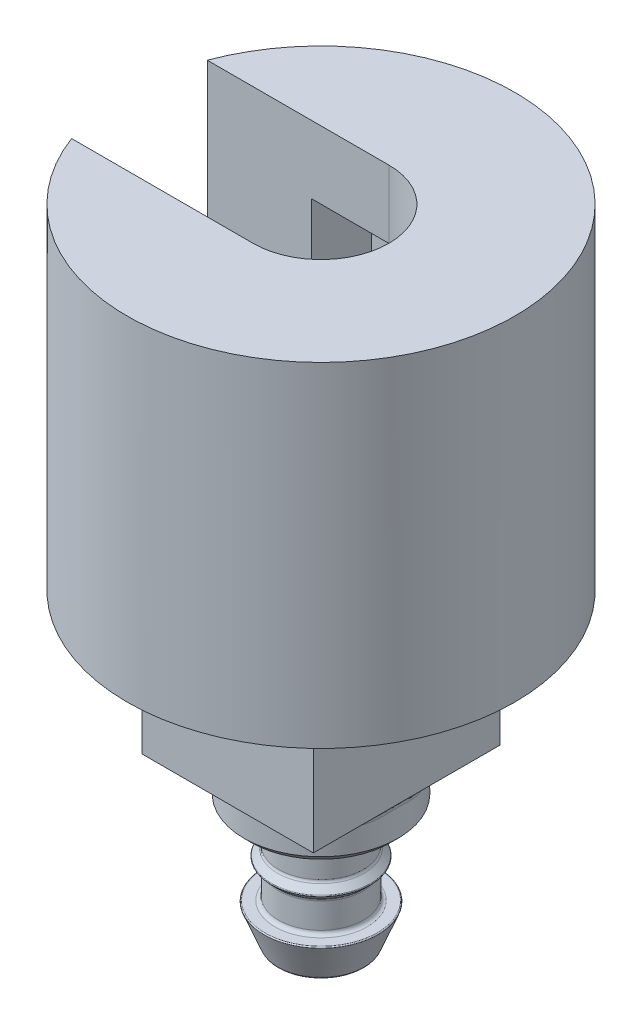
SolidWorks part; units mm, degrees
ref_plane "Front Plane" through (0, 0, 0) normal (0, 0, 1) x (1, 0, 0)
ref_plane "Top Plane" through (0, 0, 0) normal (0, 1, 0) x (1, 0, 0)
ref_plane "Right Plane" through (0, 0, 0) normal (1, 0, 0) x (0, 0, -1)
sketch "Sketch1" plane through (0, 0, 0) normal (0, 0, 1) x (1, 0, 0)
  line L0 (0, 1017.6623) -> (0, 12.7) construction
  line L1 (0, -12.7) -> (4.3656, -12.7)
  line L3 (4.3656, 0) -> (7.9375, 0)
  line L4 (7.9375, 0) -> (7.9375, 3.9688)
  line L8 (0, 3.9688) -> (0, -12.7)
  line L9 (4.3656, -12.7) -> (5.9531, -8.7312)
  line L22 (7.9375, 0) -> (7.9375, 3.9688) construction
  line L25 (7.9375, 6.35) -> (0, 6.35) construction
  line L27 (6.35, 3.9688) -> (7.9375, 3.9688)
  line L32 (5.9531, -8.7312) -> (4.3656, -8.7312)
  line L33 (4.3656, -8.7312) -> (4.3656, -5.5563)
  line L34 (4.3656, -3.9687) -> (5.1594, -4.7625)
  line L35 (5.1594, -4.7625) -> (4.3656, -5.5563)
  line L36 (5.1594, -4.7625) -> (4.3656, -4.7625) construction
  line L37 (4.3656, -3.9687) -> (4.3656, 0)
  line L38 (6.35, 3.9688) -> (0, 3.9688)
  line L40 (0, 3.9688) -> (0, -7.7377) construction
  dimension "D7" = 1.5875
  dimension "D1" = 12.7
  dimension "D2" = 3.9688
  dimension "D6" = 15.875
  dimension "D8" = 8.7312
  dimension "D10" = 7.9375
  dimension "D11" = 45
  dimension "D9" = 0.7937
revolve "Revolve1" add sketch "Sketch1" angle 360 about L0
fillet "Fillet3" radius 0.3969 5 edges at (0, -12.7, 4.3656) (0, -8.7313, 4.3656) (0, 0, 4.3656) (0, -3.9688, 4.3656) (0, -5.5562, 4.3656)
fillet "Fillet4" radius 0.0992 2 edges at (0, -8.7313, 5.9531) (0, -4.7625, 5.1594)
ref_plane "Plane1" through (0, 3.9688, 0) normal (0, 1, 0) x (1, 0, 0)
sketch "Sketch2" plane through (0, 3.9688, 0) normal (0, 1, 0) x (1, 0, 0)
  line L0 (0, 9.6273) -> (0, -9.6273) construction
  line L9 (9.0227, 0) -> (-9.0227, 0) construction
  line L11 (8.8366, 9.6273) -> (-8.8366, 9.6273)
  line L12 (8.8366, 9.6273) -> (8.8366, -9.6273)
  line L13 (8.8366, -9.6273) -> (-8.8366, -9.6273)
  line L14 (-8.8366, 9.6273) -> (-8.8366, -9.6273)
  line L15 (8.8366, 9.6273) -> (-8.8366, -9.6273) construction
  line L16 (8.8366, -9.6273) -> (-8.8366, 9.6273) construction
  point P0 (0, 0)
  point P1 (0, 0)
  point P2 (0, 0)
  point P6 (0, 0)
  point P11 (0, 0)
extrude "Boss-Extrude1" add sketch "Sketch2" along normal blind 15
sketch "Sketch3" plane through (0, -12.7, 0) normal (0, -1, 0) x (1, 0, 0)
  circle A0 centre (0, 0) radius 2.413
extrude "Cut-Extrude1" cut sketch "Sketch3" against normal blind 27
sketch "Sketch5" plane through (0, 0, 0) normal (1, 0, 0) x (0, 0, -1)
  line L0 (0, 18.9688) -> (0, 3.9688) construction
  line L1 (9.6273, 18.9688) -> (-9.6273, 18.9688) construction
  line L2 (55, 3.9688) -> (-55, 3.9688) construction
  circle A0 centre (0, 11.4688) radius 2.25
  dimension "D1" = 4.5
extrude "Cut-Extrude3" cut sketch "Sketch5" against normal blind 22.86
chamfer "Chamfer2" distance 0.762 angle 45 5 edges at (8.8366, 3.9688, 0) (0, 3.9688, -9.6273) (-8.8366, 3.9688, 0) (0, 3.9688, 9.6273) (0, 0, 7.9375)
fillet "Fillet6" radius 0.762 1 edges at (0, 3.9688, 7.9375)
sketch "Sketch7" plane through (0, 18.9688, 0) normal (0, 1, 0) x (1, 0, 0)
  circle A0 centre (0, 0) radius 20
  dimension "D1" = 40
extrude "Boss-Extrude2" add sketch "Sketch7" along normal blind 7.5
sketch "Sketch8" plane through (0, 26.4688, 0) normal (0, 1, 0) x (1, 0, 0)
  circle A0 centre (0, 0) radius 12.5
  circle A1 centre (0, 0) radius 20
  circle A2 centre (0, 0) radius 20
  dimension "D1" = 0
extrude "Boss-Extrude3" add sketch "Sketch8" along normal blind 12
ref_plane "Plane2" through (0, 38.4687, 0) normal (0, 1, 0) x (1, 0, 0)
sketch "Sketch9" plane through (0, 38.4687, 0) normal (0, 1, 0) x (1, 0, 0)
  circle A1 centre (0, 0) radius 20
  circle A2 centre (0, 0) radius 20
  dimension "D1" = 0
extrude "Boss-Extrude4" add sketch "Sketch9" along normal blind 15
sketch "Sketch10" plane through (0, 38.4687, 0) normal (0, 1, 0) x (1, 0, 0)
  line L1 (-6.5547, -10.1998) -> (5.556, -10.7764)
  line L2 (5.556, -10.7764) -> (12.1106, -0.5766)
  line L3 (12.1106, -0.5766) -> (6.5547, 10.1998)
  line L4 (6.5547, 10.1998) -> (-5.556, 10.7764)
  line L5 (-5.556, 10.7764) -> (-12.1106, 0.5766)
  line L6 (-12.1106, 0.5766) -> (-6.5547, -10.1998)
  circle A0 centre (0, 0) radius 10.5 construction
  dimension "D1" = 21
extrude "Cut-Extrude4" cut sketch "Sketch10" along normal blind 8
sketch "Sketch11" plane through (0, 0, 0) normal (1, 0, 0) x (0, 0, -1)
  line L0 (0, 53.4688) -> (0, 18.9688) construction
  line L1 (20, 53.4687) -> (-20, 53.4687) construction
  line L2 (-20, 18.9688) -> (20, 18.9688) construction
  line L3 (7, 38.4688) -> (12.5, 38.4688)
  line L5 (-7, 38.4688) -> (-7, 53.4687)
  line L6 (-7, 53.4687) -> (7, 53.4688)
  line L7 (7, 38.4688) -> (7, 53.4688)
  line L8 (-7, 38.4688) -> (7, 53.4688) construction
  line L9 (-7, 53.4687) -> (7, 38.4688) construction
  line L10 (-12.5, 28.4688) -> (12.5, 28.4688)
  line L11 (-12.5, 28.4688) -> (-12.5, 38.4688)
  line L12 (-12.5, 38.4688) -> (-7, 38.4688)
  line L13 (12.5, 28.4688) -> (12.5, 38.4688)
  line L14 (-12.5, 28.4688) -> (12.5, 38.4688) construction
  line L15 (-12.5, 38.4688) -> (12.5, 28.4688) construction
  point P6 (0, 45.9688)
  point P11 (0, 33.4688)
  dimension "D1" = 14
  dimension "D3" = 10
  dimension "D4" = 25
extrude "Cut-Extrude5" cut sketch "Sketch11" against normal through all
sketch "Sketch12" plane through (0, 53.4687, 0) normal (0, 1, 0) x (1, 0, 0)
  circle A0 centre (0, 0) radius 7
  dimension "D1" = 14
extrude "Cut-Extrude6" cut sketch "Sketch12" against normal blind 12 and the other way through all
